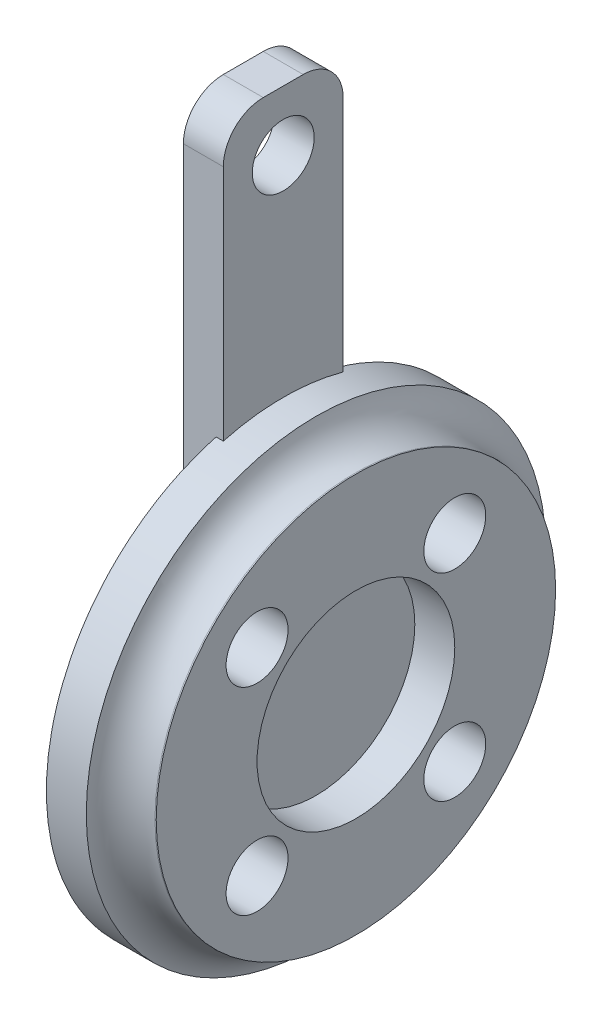
SolidWorks part; units mm, degrees
material "PLA"
ref_plane "Front Plane" through (0, 0, 0) normal (1, 0, 0) x (0, 1, 0)
ref_plane "Top Plane" through (0, 0, 0) normal (0, 0, 1) x (0, 1, 0)
ref_plane "Right Plane" through (0, 0, 0) normal (0, 1, 0) x (-1, 0, 0)
sketch "Sketch1" plane through (0, 0, 0) normal (1, 0, 0) x (0, 1, 0)
  circle A0 centre (0, 0) radius 11.5
  circle A1 centre (0, 0) radius 10.5
  dimension "D1" = 1
  dimension "D2" = 21
extrude "Boss-Extrude1" add sketch "Sketch1" along normal blind 2
extrude "Boss-Extrude2" add sketch "Sketch1<2>" along normal up to surface (2 mm away) contours A1 region at (0, 0, 0) up to face at (2, 0, -11.5)
sketch "Sketch1<2>" plane through (0, 0, 0) normal (1, 0, 0) x (0, 1, 0) same geometry as "Sketch1"
ref_plane "Plane1" through (-1.64, 0, 0) normal (-1, 0, 0) x (0, 0, 1)
sketch "Sketch2" plane through (-1.64, 0, 0) normal (-1, 0, 0) x (0, 0, 1)
  line L1 (-3, -5) -> (3, -5)
  line L2 (-3, -5) -> (-3, 5)
  line L3 (-3, 5) -> (3, 5)
  line L4 (3, -5) -> (3, 5)
  line L5 (0, 5) -> (0, -5) construction
  line L6 (-3, 0) -> (3, 0) construction
  point P0 (0, 0)
  dimension "D1" = 6
  dimension "D2" = 10
sketch "Sketch3" plane through (0, 0, 0) normal (-1, 0, 0) x (0, -1, 0)
  circle A0 centre (0, 0) radius 11.5
  circle A1 centre (0, 0) radius 9.5
  circle A2 centre (0, 0) radius 11.5 construction
  dimension "D1" = 2
extrude "Cut-Extrude2" cut sketch "Sketch3" against normal blind 1.5 contours A1 region at (0, 0, 0)
sketch "Sketch4" plane through (0, 0, 0) normal (-1, 0, 0) x (0, -1, 0)
  circle A1 centre (0, 0) radius 11.5
  circle A2 centre (0, 0) radius 11.5
  dimension "D1" = 0
loft "Loft1" add profiles "Sketch4", "Sketch2" connector at (0, 0, 11.5) connector at (-1.64, -5, -3)
sketch "Sketch6" plane through (-1.64, 0, 0) normal (-1, 0, 0) x (0, -1, 0)
  line L0 (0, 0) -> (-22, 0) construction
  line L1 (5, 3) -> (-25, 3)
  line L2 (-25, 3) -> (-25, -3)
  line L3 (-25, -3) -> (5, -3)
  line L4 (5, -3) -> (5, 3)
  circle A1 centre (-22, 0) radius 1.55
  dimension "D2" = 3.1
  dimension "D1" = 22
  dimension "D3" = 3
extrude "Boss-Extrude3" add sketch "Sketch6" against normal blind 2
sketch "Sketch7" plane through (2, 0, 0) normal (1, 0, 0) x (0, 1, 0)
  line L0 (0, 25.0823) -> (0, -32.3177) construction
  line L1 (-4.95, 4.95) -> (4.95, 4.95) construction
  line L2 (15.5615, 0) -> (-15.5615, 0) construction
  line L3 (4.95, 4.95) -> (4.95, -4.95) construction
  line L4 (-4.95, 4.95) -> (-4.95, -4.95) construction
  line L5 (-4.95, -4.95) -> (4.95, -4.95) construction
  circle A0 centre (0, 0) radius 10
  circle A1 centre (-4.95, 4.95) radius 1
  circle A2 centre (4.95, 4.95) radius 1
  circle A3 centre (4.95, -4.95) radius 1
  circle A4 centre (-4.95, -4.95) radius 1
  circle A5 centre (0, 0) radius 4.95
  dimension "D1" = 20
  dimension "D2" = 2
  dimension "D3" = 9.9
extrude "Boss-Extrude4" add sketch "Sketch7" along normal blind 2
fillet "Fillet1" radius 2 1 edges at (2, 0, -10)
fillet "Fillet2" radius 2 2 edges at (-0.64, 25, 3) (-0.64, 25, -3)
sketch "Sketch8" plane through (4, 0, 0) normal (1, 0, 0) x (0, 1, 0)
  circle A0 centre (-4.95, -4.95) radius 1 construction
  circle A1 centre (4.95, -4.95) radius 1 construction
  circle A2 centre (4.95, 4.95) radius 1 construction
  circle A3 centre (-4.95, 4.95) radius 1 construction
  circle A4 centre (-4.95, -4.95) radius 1
  circle A5 centre (4.95, -4.95) radius 1
  circle A6 centre (4.95, 4.95) radius 1
  circle A7 centre (-4.95, 4.95) radius 1
  circle A8 centre (4.95, 4.95) radius 1.55
  circle A9 centre (-4.95, 4.95) radius 1.55
  circle A10 centre (-4.95, -4.95) radius 1.55
  circle A11 centre (4.95, -4.95) radius 1.55
  circle A12 centre (-4.95, 4.95) radius 2.55
  circle A13 centre (4.95, 4.95) radius 2.55
  circle A14 centre (-4.95, -4.95) radius 2.55
  circle A15 centre (4.95, -4.95) radius 2.55
  circle M1 centre (-4.95, -4.95) radius 1
  circle M2 centre (4.95, 4.95) radius 1
  circle M4 centre (-4.95, 4.95) radius 1
  circle M5 centre (4.95, -4.95) radius 1
  dimension "D1" = 3.1
  dimension "D2" = 1
extrude "Cut-Extrude3" cut sketch "Sketch8" against normal through all both and the other way through all contours A9 M4 | A8 M2 | M2 | M4 | M1 | A10 M1 | M5 | A11 M5 region at (4, -4.95, -4.95) region at (4, 4.95, -4.95) region at (4, 4.95, 4.95) region at (4, -4.95, 4.95) region at (4, 3.4438, 4.95) region at (4, -6.4562, 4.95) region at (4, -6.4562, -4.95) region at (4, 3.4438, -4.95)
sketch "Sketch9" plane through (1.5, 0, 0) normal (-1, 0, 0) x (0, -1, 0)
  circle A1 centre (0, 0) radius 9.5
  circle A2 centre (0, 0) radius 9.5
  circle M2 centre (-4.95, -4.95) radius 1.55
  circle M3 centre (4.95, -4.95) radius 1.55
  circle M4 centre (4.95, 4.95) radius 1.55
  circle M5 centre (-4.95, 4.95) radius 1.55
  circle M6 centre (0, 0) radius 9.5
  dimension "D1" = 0
extrude "Boss-Extrude5" add sketch "Sketch9" along normal up to surface (1.5 mm away) contours M6 M3 M5 M4 M2 region at (1.5, 0, 0) up to face at (0, 4.95, -3.4)
extrude "Cut-Extrude4" cut sketch "Sketch8<3>" along normal offset from surface 3 and the other way through all from surface contours A15 | A13 | A12 | A14 up to face at (4, 4.95, -6.5) starting at face at (-1.64, 12.1036, -0.375)
sketch "Sketch8<3>" plane through (4, 0, 0) normal (1, 0, 0) x (0, 1, 0) same geometry as "Sketch8"
fillet "Fillet3" radius 10 2 edges at (-1.4024, 6.5932, -3) (-1.4024, 6.5932, 3)
